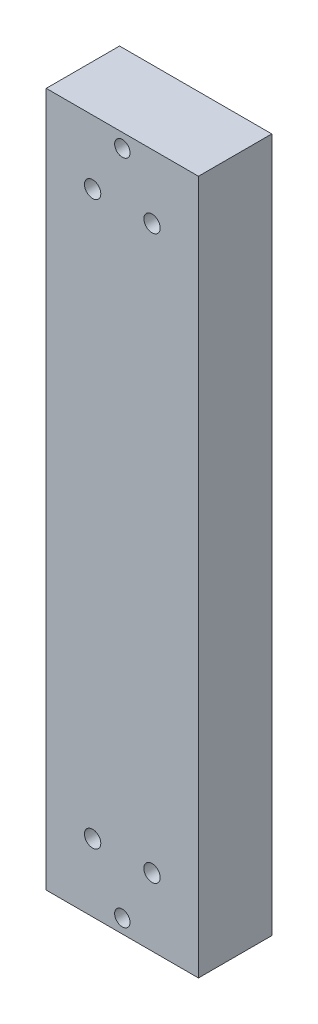
SolidWorks part; units mm, degrees
ref_plane "Front Plane" through (0, 0, 0) normal (0, 0, 1) x (1, 0, 0)
ref_plane "Top Plane" through (0, 0, 0) normal (0, 1, 0) x (1, 0, 0)
ref_plane "Right Plane" through (0, 0, 0) normal (1, 0, 0) x (0, 0, -1)
sketch "Sketch1" plane through (0, 0, 0) normal (0, 0, 1) x (1, 0, 0)
  line L1 (-6.5, -86.5) -> (6.5, -86.5)
  line L2 (-6.5, -86.5) -> (-6.5, 85.5)
  line L3 (-6.5, 85.5) -> (6.5, 85.5)
  line L4 (6.5, -86.5) -> (6.5, 85.5)
  line L5 (6.5, -84.5) -> (6.5, 84.5) construction
  line L6 (6.5, -86.5) -> (9.5, 85.5) construction
  line L7 (9.5, -86.5) -> (22.5, -86.5)
  line L8 (9.5, -86.5) -> (9.5, 85.5)
  line L9 (9.5, 85.5) -> (22.5, 85.5)
  line L10 (22.5, -86.5) -> (22.5, 85.5)
  line L11 (-12.5, -86.5) -> (28.5, -86.5)
  line L12 (-12.5, -94) -> (28.5, -94)
  line L13 (-12.5, -94) -> (-12.5, 93)
  line L14 (-12.5, 93) -> (28.5, 93)
  line L15 (28.5, -94) -> (28.5, 93)
  line L16 (-12.5, -94) -> (28.5, 93) construction
  line L17 (-12.5, 93) -> (28.5, -94) construction
  line L18 (-12.5, 85.5) -> (28.5, 85.5)
  line L19 (-10.5, -86.5) -> (-10.5, 85.5)
  line L20 (26.5, -86.5) -> (26.5, 85.5)
  line L21 (8, -94) -> (8, -86.5) construction
  line L22 (28.5, -0.5) -> (-12.5, -0.5) construction
  line L24 (-6.5, 84.5) -> (6.5, 84.5) construction
  line L25 (22.5, -84.5) -> (22.5, 84.5) construction
  line L26 (-6.5, -84.5) -> (-6.5, 84.5) construction
  line L27 (9.5, -84.5) -> (9.5, 84.5) construction
  line L28 (-6.5, -84.5) -> (6.5, -84.5) construction
  circle A0 centre (0, -75.75) radius 2.2
  circle A1 centre (16, -75.75) radius 2.2
  circle A2 centre (0, 75.75) radius 2.2
  circle A3 centre (16, 75.75) radius 2.2
  circle A4 centre (8, -90.25) radius 2.075
  circle A5 centre (8, 89.25) radius 2.075
  circle A6 centre (16, -75.75) radius 3 construction
  point P26 (8, -0.5)
  dimension "D3" = 4.15
  dimension "D8" = 4.4
  dimension "D1" = 6
  dimension "D2" = 7.5
  dimension "D4" = 2
  dimension "D5" = 2
  dimension "D6" = 1
  dimension "D7" = 2
extrude "Boss-Extrude1" add sketch "Sketch1" along normal blind 4.75 contours A2 | A3 | A0 | A1 | L13 L14 L15 L12 | A5 | A4 region at (0, -75.75, 0) region at (16, -75.75, 0) region at (0, 75.75, 0) region at (16, 75.75, 0)
extrude "Boss-Extrude2" add sketch "Sketch1<3>" against normal offset from surface (15 mm away) 2 contours L13 L18 L3 L9 L15 L14 A5 | L11 L19 L18 L13 | L12 L15 L11 L7 L1 L13 A4 | L20 L11 L15 L18 | L18 L4 L11 L8 region at (0, -86.9168, 0) region at (8, -0.5, 0) region at (-8.5, 85.9168, 0) region at (-11.5, -0.5, 0) region at (27.5, -0.5, 0) offset beyond the face yes
sketch "Sketch1<3>" plane through (0, 0, 0) normal (0, 0, 1) x (1, 0, 0) same geometry as "Sketch1"
equation "\"D5@Sketch1\"=\"D4@Sketch1\""
